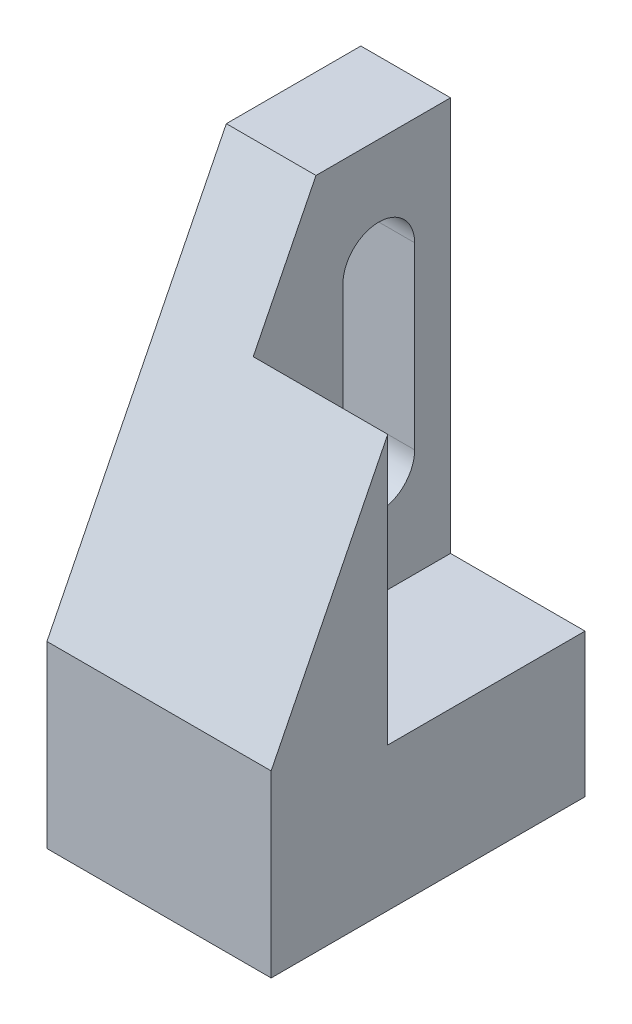
SolidWorks part; units mm, degrees
ref_plane "Front Plane" through (0, 0, 0) normal (1, 0, 0) x (0, 1, 0)
ref_plane "Top Plane" through (0, 0, 0) normal (0, 0, 1) x (0, 1, 0)
ref_plane "Right Plane" through (0, 0, 0) normal (0, 1, 0) x (-1, 0, 0)
sketch "Sketch1" plane through (0, 0, 0) normal (1, 0, 0) x (0, 1, 0)
  line L0 (0, -28.7324) -> (0, 28.7324) construction
  line L1 (-10, 0) -> (10, 0) construction
  line L2 (-10, 4) -> (10, 4)
  line L3 (-10, -4) -> (10, -4)
  line L4 (-38, -8) -> (22, -8)
  line L5 (22, -8) -> (22, 7)
  line L6 (22, 7) -> (-18, 27)
  line L7 (-18, 27) -> (-38, 27)
  line L8 (-38, 27) -> (-38, -8)
  line L9 (-22, -8) -> (-22, 14)
  line L10 (-22, 14) -> (8, 14)
  arc A0 (-10, 4) -> (-10, -4) centre (-10, 0) ccw
  arc A1 (10, -4) -> (10, 4) centre (10, 0) ccw
  point P4 (0, 0)
  point P7 (0, 0)
  dimension "D2" = 4
  dimension "D1" = 20
  dimension "D3" = 35
  dimension "D4" = 8
  dimension "D5" = 15
  dimension "D6" = 38
  dimension "D7" = 20
  dimension "D8" = 44
  dimension "D9" = 60
  dimension "D10" = 22
extrude "Boss-Extrude1" add sketch "Sketch1" along normal blind 25 contours L9 L10 L6 L7 L8 L4 region at (0, -24.8621, 12.1438)
extrude "Boss-Extrude2" add sketch "Sketch1<3>" along normal blind 25 contours L10 L9 L4 L5 L6 A1 L3 A0 L2 region at (0, -21.5081, 3)
sketch "Sketch1<3>" plane through (0, 0, 0) normal (1, 0, 0) x (0, 1, 0) same geometry as "Sketch1"
extrude "Cut-Extrude1" cut sketch "Sketch1<4>" against normal blind 15 from offset 25 contours L10 L9 L4 L5 L6 A1 L3 A0 L2 region at (0, -21.5081, 3)
sketch "Sketch1<4>" plane through (0, 0, 0) normal (1, 0, 0) x (0, 1, 0) same geometry as "Sketch1"
